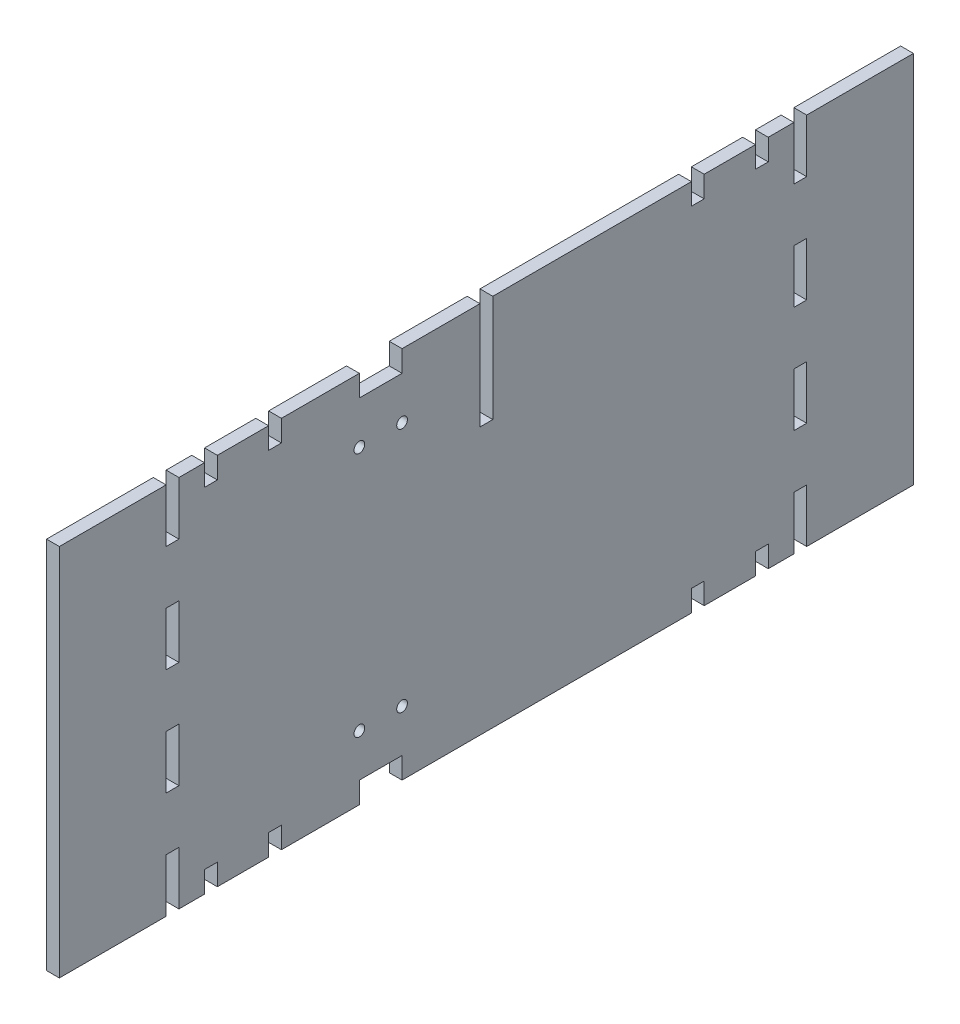
SolidWorks part; units mm, degrees
ref_plane "Front" through (0, 0, 0) normal (0, 0, 1) x (1, 0, 0)
ref_plane "Top" through (0, 0, 0) normal (0, 1, 0) x (1, 0, 0)
ref_plane "Right" through (0, 0, 0) normal (1, 0, 0) x (0, 0, -1)
sketch "Sketch1" plane through (0, 0, 0) normal (1, 0, 0) x (0, 0, -1)
  line L1 (0, 0) -> (-400, 0)
  line L2 (0, 0) -> (0, 175)
  line L3 (0, 175) -> (-400, 175)
  line L4 (-400, 0) -> (-400, 175)
  dimension "D1" = 400
  dimension "D2" = 175
extrude "Boss-Extrude1" add sketch "Sketch1" along normal blind 6
sketch "Sketch3" plane through (6, 0, 0) normal (1, 0, 0) x (0, 0, -1)
  line L0 (-400, 175) -> (-400, 0) construction
  line L1 (-350, 175) -> (-344, 175)
  line L2 (-350, 175) -> (-350, 150)
  line L3 (-350, 150) -> (-344, 150)
  line L4 (-344, 175) -> (-344, 150)
  line L5 (0, 175) -> (-400, 175) construction
  dimension "D1" = 6
  dimension "D2" = 25
  dimension "D3" = 50
extrude "Cut-Extrude1" cut sketch "Sketch3" against normal through all
pattern_linear "LPattern1" count 2 spacing 294 along (0, 0, -1) count 4 spacing 50 along (0, -1, 0) of "Cut-Extrude1"
sketch "Sketch4" plane through (6, 0, 0) normal (1, 0, 0) x (0, 0, -1)
  line L0 (-56, 175) -> (-344, 175) construction
  line L1 (-332, 175) -> (-326, 175)
  line L2 (-332, 175) -> (-332, 165)
  line L3 (-332, 165) -> (-326, 165)
  line L4 (-326, 175) -> (-326, 165)
  line L5 (-344, 150) -> (-344, 175) construction
  dimension "D1" = 6
  dimension "D2" = 12
  dimension "D3" = 10
extrude "Cut-Extrude2" cut sketch "Sketch4" against normal through all
pattern_linear "LPattern2" count 2 spacing 258 along (0, 0, -1) count 2 spacing 165 along (0, -1, 0) of "Cut-Extrude2"
sketch "Sketch5" plane through (6, 0, 0) normal (1, 0, 0) x (0, 0, -1)
  line L0 (-74, 175) -> (-326, 175) construction
  line L1 (-302, 175) -> (-296, 175)
  line L2 (-302, 175) -> (-302, 165)
  line L3 (-302, 165) -> (-296, 165)
  line L4 (-296, 175) -> (-296, 165)
  line L5 (-326, 165) -> (-326, 175) construction
  line L6 (-332, 165) -> (-326, 165) construction
  dimension "D1" = 24
  dimension "D2" = 6
extrude "Cut-Extrude3" cut sketch "Sketch5" against normal through all
pattern_linear "LPattern3" count 2 spacing 165 along (0, -1, 0) count 2 spacing 198 along (0, 0, -1) of "Cut-Extrude3"
sketch "Sketch6" plane through (6, 0, 0) normal (1, 0, 0) x (0, 0, -1)
  line L0 (-104, 175) -> (-296, 175) construction
  line L1 (-203, 175) -> (-197, 175)
  line L2 (-203, 175) -> (-203, 125)
  line L3 (-203, 125) -> (-197, 125)
  line L4 (-197, 175) -> (-197, 125)
  point P6 (-200, 175)
  point P7 (-200, 175)
  dimension "D1" = 6
  dimension "D2" = 50
extrude "Cut-Extrude4" cut sketch "Sketch6" against normal blind 10
sketch "Sketch7" plane through (6, 0, 0) normal (1, 0, 0) x (0, 0, -1)
  line L0 (-203, 175) -> (-296, 175) construction
  line L1 (-259.5, 175) -> (-239.5, 175)
  line L2 (-259.5, 175) -> (-259.5, 165)
  line L3 (-259.5, 165) -> (-239.5, 165)
  line L4 (-239.5, 175) -> (-239.5, 165)
  point P6 (-249.5, 175)
  point P7 (-249.5, 175)
  dimension "D1" = 10
  dimension "D2" = 20
extrude "Cut-Extrude5" cut sketch "Sketch7" against normal blind 10
pattern_linear "LPattern4" count 2 spacing 165 along (0, -1, 0) of "Cut-Extrude5"
sketch "Sketch8" plane through (6, 0, 0) normal (1, 0, 0) x (0, 0, -1)
  line L0 (-259.5, 145) -> (-239.5, 145) construction
  line L1 (-259.5, 30) -> (-239.5, 30) construction
  line L2 (-249.5, 165) -> (-249.5, 10) construction
  line L3 (-259.5, 165) -> (-239.5, 165) construction
  line L4 (-239.5, 10) -> (-259.5, 10) construction
  circle A0 centre (-259.5, 145) radius 2.5
  circle A1 centre (-239.5, 145) radius 2.5
  circle A2 centre (-259.5, 30) radius 2.5
  circle A3 centre (-239.5, 30) radius 2.5
  point P8 (-249.5, 145)
  point P15 (-249.5, 30)
  dimension "D3" = 5
  dimension "D1" = 20
  dimension "D2" = 20
  dimension "D4" = 20
extrude "Cut-Extrude6" cut sketch "Sketch8" against normal blind 10
